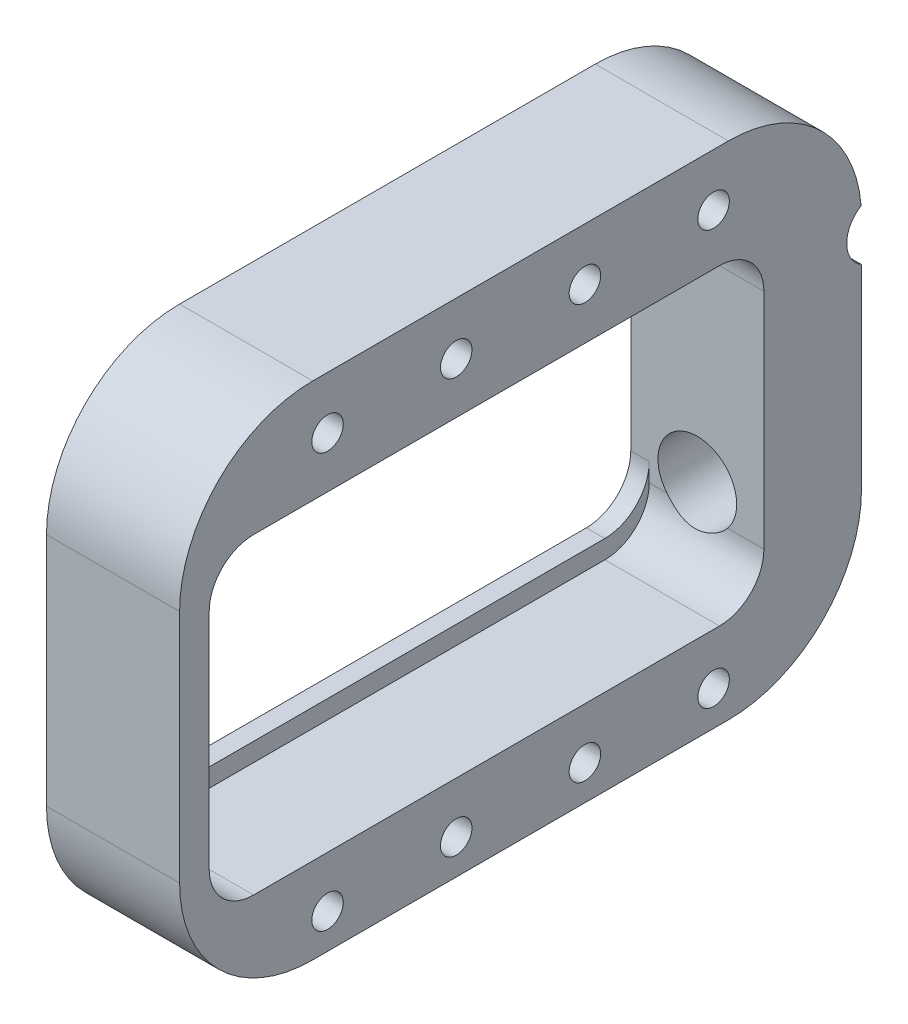
SolidWorks part; units mm, degrees
material "6061-T6 (SS)"
ref_plane "Front Plane" through (0, 0, 0) normal (0, 0, 1) x (1, 0, 0)
ref_plane "Top Plane" through (0, 0, 0) normal (0, 1, 0) x (1, 0, 0)
ref_plane "Right Plane" through (0, 0, 0) normal (1, 0, 0) x (0, 0, -1)
sketch "Sketch1" plane through (0, 0, 0) normal (1, 0, 0) x (0, 0, -1)
  line L0 (0, 22.2885) -> (0, -22.2885) construction
  line L1 (-26.3525, 22.2885) -> (32.1945, 22.2885)
  line L2 (-26.3525, 22.2885) -> (-26.3525, -22.2885)
  line L3 (-26.3525, -22.2885) -> (32.1945, -22.2885)
  line L4 (32.1945, 22.2885) -> (32.1945, -22.2885)
  line L5 (-23.8125, 13.3985) -> (23.8125, 13.3985)
  line L6 (-23.8125, 13.3985) -> (-23.8125, -13.3985)
  line L7 (-23.8125, -13.3985) -> (23.8125, -13.3985)
  line L8 (23.8125, 13.3985) -> (23.8125, -13.3985)
  line L9 (23.8125, -13.3985) -> (-23.8125, 13.3985) construction
  dimension "D1" = 8.89
  dimension "D2" = 2.54
  dimension "D3" = 47.625
  dimension "D4" = 26.797
  dimension "D5" = 8.382
  dimension "D6" = 8.89
extrude "Boss-Extrude1" add sketch "Sketch1" along normal mid plane 11.43
sketch "Sketch9" plane through (0, 0, -23.8125) normal (0, 0, 1) x (1, 0, 0)
  line L0 (-5.715, 13.3985) -> (-5.715, 11.811)
  line L1 (-5.715, -13.3985) -> (-4.1275, -13.3985)
  line L2 (-5.715, -13.3985) -> (-5.715, -11.811)
  line L3 (-5.715, -11.811) -> (-4.1275, -11.811)
  line L4 (-4.1275, -13.3985) -> (-4.1275, -11.811)
  line L5 (-5.715, 13.3985) -> (-4.1275, 13.3985)
  line L6 (-5.715, 11.811) -> (-4.1275, 11.811)
  line L7 (-4.1275, 13.3985) -> (-4.1275, 11.811)
  line L9 (-5.715, -13.3985) -> (-5.715, 13.3985) construction
  dimension "D1" = 23.622
  dimension "D2" = 1.5875
extrude "Boss-Extrude2" add sketch "Sketch9" along normal up to next
fillet "Fillet11" radius 3.81 4 edges at (-4.9213, -11.811, -23.8125) (-4.9212, 11.811, -23.8125) (-4.9213, -11.811, 23.8125) (-4.9212, 11.811, 23.8125)
fillet "Fillet12" radius 3.81 4 edges at (0.7937, 13.3985, 23.8125) (0.7937, -13.3985, 23.8125) (0.7938, -13.3985, -23.8125) (0.7937, 13.3985, -23.8125)
sketch "Sketch21" plane through (5.715, 0, 0) normal (1, 0, 0) x (0, 0, -1)
  line L1 (32.1945, 22.2885) -> (-26.3525, 22.2885) construction
  line L4 (32.1945, -22.2885) -> (32.1945, 22.2885) construction
  circle A0 centre (33.4645, 9.5885) radius 2.54
  dimension "D1" = 5.08
  dimension "D3" = 1.27
  dimension "D2" = 12.7
extrude "Cut-Extrude3" cut sketch "Sketch21" against normal blind 1.27
hole_wizard "1/4 Clearance Hole1" positions "Sketch5" profile "Sketch4" hole size "1/4" standard "ANSI Inch"
sketch "Sketch5" plane through (-2.5308, 6.493, -32.1945) normal (0, 0, 1) x (1, 0, 0)
  line L12 (8.2458, 15.7955) -> (8.2458, -28.7815) construction
  line L16 (-3.1842, -19.8915) -> (8.2458, -19.8915) construction
  line L17 (-3.1842, 15.7955) -> (-3.1842, -28.7815) construction
  line L30 (2.5308, -19.8915) -> (2.5308, -13.9225) construction
  line L32 (8.2458, -28.7815) -> (8.2458, 0.8958) construction
  point P0 (2.5308, -13.9225)
  dimension "D2" = 5.969
sketch "Sketch4" plane through (0, -7.4295, -32.1945) normal (1, 0, 0) x (0, 1, 0)
  line L0 (0, 0) -> (0, 10.9198)
  line L1 (0, 10.9198) -> (3.3782, 8.89)
  line L2 (3.3782, 8.89) -> (3.3782, 0)
  line L5 (3.3782, 0) -> (0, 0)
  line L10 (0, 10.9198) -> (-3.3782, 8.89) construction
  line L11 (0, -6.35) -> (0, 107.95) construction
  dimension "Hole Dia." = 6.7564
  dimension "Hole Depth" = 8.89
  dimension "Drill Angle" = 118
sketch "Sketch14" plane through (-5.715, 0, 0) normal (-1, 0, 0) x (0, 0, 1)
  line L0 (-32.1945, -17.78) -> (-19.4945, -17.78) construction
  line L1 (-32.1945, 17.78) -> (-19.4945, 17.78) construction
  line L2 (-19.4945, 17.78) -> (-8.4455, 17.78) construction
  line L3 (13.6525, 17.78) -> (26.3525, 17.78) construction
  line L4 (-19.4945, -17.78) -> (-8.4455, -17.78) construction
  line L5 (13.6525, -17.78) -> (26.3525, -17.78) construction
  line L6 (-19.1091, 17.78) -> (-19.1091, 22.2885) construction
  line L7 (-7.0267, -17.78) -> (-7.0267, -22.2885) construction
  line L8 (-8.4455, -17.78) -> (2.6035, -17.78) construction
  line L9 (2.6035, -17.78) -> (13.6525, -17.78) construction
  line L10 (2.6035, 17.78) -> (13.6525, 17.78) construction
  line L11 (-8.4455, 17.78) -> (2.6035, 17.78) construction
  line L12 (26.3525, -22.2885) -> (-32.1945, -22.2885) construction
  line L13 (-32.1945, 22.2885) -> (26.3525, 22.2885) construction
  line L14 (26.3525, 22.2885) -> (26.3525, -22.2885) construction
  line L15 (-32.1945, -22.2885) -> (-32.1945, 22.2885) construction
  point P0 (-19.4945, 17.78)
  point P1 (-19.4945, -17.78)
  point P2 (13.6525, -17.78)
  point P3 (13.6525, 17.78)
  dimension "D1" = 12.7
  dimension "D2" = 35.56
hole_wizard "#6-32 Tapped Hole1" positions "Sketch16" profile "Sketch15" tap size "#6-32" standard "ANSI Inch" end condition through all
sketch "Sketch16" plane through (5.715, 17.9556, 19.2123) normal (-1, 0, 0) x (0, 0, 1)
  point P0 (-27.6578, -0.1756)
  point P3 (-16.6088, -0.1756)
  point P6 (-5.5598, -0.1756)
  point P9 (-38.7068, -0.1756)
  point P12 (-38.7068, -35.7356)
  point P15 (-27.6578, -35.7356)
  point P18 (-16.6088, -35.7356)
  point P21 (-5.5598, -35.7356)
cosmetic thread "Hole Thread1" parameters "D2"=3.5052
cosmetic thread "Hole Thread2" parameters "D2"=3.5052
cosmetic thread "Hole Thread3" parameters "D2"=3.5052
cosmetic thread "Hole Thread4" parameters "D2"=3.5052
cosmetic thread "Hole Thread5" parameters "D2"=3.5052
cosmetic thread "Hole Thread6" parameters "D2"=3.5052
cosmetic thread "Hole Thread7" parameters "D2"=3.5052
cosmetic thread "Hole Thread8" parameters "D2"=3.5052
sketch "Sketch15" plane through (5.715, 17.78, -8.4455) normal (0, 1, 0) x (0, 0, -1)
  line L0 (0, 0) -> (0, 11.43)
  line L1 (0, 11.43) -> (1.3525, 11.43)
  line L2 (1.3525, 11.43) -> (1.3525, 0)
  line L5 (1.3525, 0) -> (0, 0)
  line L11 (0, -6.35) -> (0, 107.95) construction
  dimension "Thru Tap Drill Dia." = 2.7051
  dimension "Thru Tap Drill Depth" = 11.43
sketch "Sketch22" plane through (5.715, 0, 0) normal (1, 0, 0) x (0, 0, -1)
  line L0 (-26.3525, 22.2885) -> (-26.3525, -22.2885) construction
  line L1 (-26.3525, -28.2057) -> (32.1945, -28.2057)
  line L2 (-26.3525, -28.2057) -> (-26.3525, -20.7645)
  line L3 (-26.3525, -20.7645) -> (32.1945, -20.7645)
  line L4 (32.1945, -28.2057) -> (32.1945, -20.7645)
  line L5 (-26.3525, -28.2057) -> (32.1945, -20.7645) construction
  line L6 (-26.3525, -20.7645) -> (32.1945, -28.2057) construction
  line L7 (32.1945, -22.2885) -> (32.1945, 7.3888) construction
  line L8 (-26.3525, -22.2885) -> (32.1945, -22.2885) construction
  point P4 (2.921, -24.4851)
  dimension "D1" = 1.524
extrude "Cut-Extrude4" cut sketch "Sketch22" against normal through all
fillet "Fillet13" radius 11.43 2 edges at (0, 22.2885, -32.1945) (0, -20.7645, -32.1945)
fillet "Fillet14" radius 11.43 2 edges at (0, 22.2885, 26.3525) (0, -20.7645, 26.3525)
sketch "Sketch11" plane through (5.715, 0, 0) normal (1, 0, 0) x (0, 0, -1)
  line L0 (32.1945, -9.3345) -> (32.1945, 7.3888) construction
  line L1 (32.1945, 16.2163) -> (30.861, 16.2163)
  line L2 (32.1945, 16.2163) -> (32.1945, -14.6923)
  line L3 (32.1945, -14.6923) -> (30.861, -14.6923)
  line L4 (30.861, 16.2163) -> (30.861, -14.6923)
  arc A1 (32.1583, 11.7669) -> (20.7645, 22.2885) centre (20.7645, 10.8585) ccw construction
  arc A2 (20.7645, -20.7645) -> (32.1945, -9.3345) centre (20.7645, -9.3345) ccw construction
  dimension "D1" = 30.861
extrude "Cut-Extrude2" [suppressed] cut sketch "Sketch11" against normal blind 1.016
ref_point "Point1" [suppressed]
sketch "Sketch17" plane through (-5.715, 0, 0) normal (-1, 0, 0) x (0, 0, 1)
  line L0 (-44.2595, 38.862) -> (-44.2595, -37.338)
  line L1 (-44.2595, 38.862) -> (116.0145, 38.862)
  line L2 (-44.2595, -37.338) -> (116.0145, -37.338)
  line L3 (116.0145, 38.862) -> (116.0145, -37.338)
  line L4 (45.4025, 22.2885) -> (45.4025, -20.7645) construction
  line L5 (45.4025, 22.2885) -> (103.9495, 22.2885) construction
  line L6 (45.4025, -20.7645) -> (103.9495, -20.7645) construction
  line L7 (103.9495, 22.2885) -> (103.9495, -20.7645) construction
  line L8 (-32.1945, 0.762) -> (26.3525, 0.762) construction
  line L10 (26.3525, 10.8585) -> (26.3525, -9.3345) construction
  line L11 (-32.1945, 0.762) -> (-44.2595, 0.762) construction
  line L12 (-20.7645, 22.2885) -> (14.9225, 22.2885) construction
  line L14 (103.9495, 0.762) -> (116.0145, 0.762) construction
  line L15 (-44.2595, -37.338) -> (-40.3225, -41.275) construction
  line L16 (-40.3225, -41.275) -> (112.0775, -41.275) construction
  line L17 (112.0775, -41.275) -> (116.0145, -37.338) construction
  line L18 (-40.3225, -41.275) -> (-40.3225, -37.338) construction
  line L19 (112.0775, -41.275) -> (112.0775, -37.338) construction
  line L20 (26.3525, 10.8585) -> (26.3525, -9.3345) construction
  line L21 (-32.1945, -9.3345) -> (-32.1945, 10.8585) construction
  line L22 (-20.7645, -20.7645) -> (14.9225, -20.7645) construction
  dimension "D1" = 19.05
  dimension "D2" = 76.2
  dimension "D3" = 152.4
  dimension "D4" = 12.065
extrude "Maching Stock" [suppressed] add sketch "Sketch17" against normal blind 12.7 separate body
sketch "Sketch19" [suppressed] plane through (-5.715, 0, 0) normal (-1, 0, 0) x (0, 0, 1)
  line L0 (-8.001, 35.0972) -> (-8.001, -32.2156) construction
  line L1 (-8.001, -32.2156) -> (2.159, -32.2156) construction
  line L2 (2.159, -32.2156) -> (2.159, 32.3464) construction
  line L3 (34.7223, 0.127) -> (-40.8428, 0.127) construction
  line L4 (26.3525, -9.3345) -> (26.3525, 10.8585)
  line L5 (14.9225, 22.2885) -> (-20.7645, 22.2885)
  line L6 (-32.1945, 10.8585) -> (-32.1945, -9.3345)
  line L7 (-20.7645, -20.7645) -> (14.9225, -20.7645)
  line L8 (26.3525, -9.3345) -> (26.3525, -10.033)
  line L9 (14.9225, 22.2885) -> (2.159, 22.2885)
  line L10 (-32.1945, 10.8585) -> (-32.1945, 0.127)
  line L11 (-20.7645, -20.7645) -> (14.9225, -20.7645)
  line L12 (-40.8428, 0.127) -> (-40.8428, -10.033) construction
  line L13 (-40.8428, -10.033) -> (36.1785, -10.033) construction
  line L14 (2.159, -22.2885) -> (14.9225, -22.2885)
  line L15 (-8.001, 22.2885) -> (-20.7645, 22.2885)
  line L16 (26.3525, 0.127) -> (26.3525, 10.8585)
  line L17 (-32.1945, -10.033) -> (-32.1945, 0.6985)
  arc A3 (-32.1945, -9.3345) -> (-20.7645, -20.7645) centre (-20.7645, -9.3345) ccw
  arc A4 (26.3525, 10.8585) -> (14.9225, 22.2885) centre (14.9225, 10.8585) ccw
  arc A5 (-20.7645, 22.2885) -> (-32.1945, 10.8585) centre (-20.7645, 10.8585) ccw
  arc A6 (-32.1945, -9.3345) -> (-20.7645, -20.7645) centre (-20.7645, -9.3345) ccw
  arc A8 (26.3525, 10.8585) -> (14.9225, 22.2885) centre (14.9225, 10.8585) ccw
  arc A9 (-20.7645, 22.2885) -> (-32.1945, 10.8585) centre (-20.7645, 10.8585) ccw
  arc A10 (14.9225, -20.7645) -> (26.3525, -9.3345) centre (14.9225, -9.3345) ccw
  arc A11 (14.9225, -20.7645) -> (26.3525, -9.3345) centre (14.9225, -9.3345) ccw
  dimension "D2" = 10.16
  dimension "D1" = 0
sketch "Sketch20" plane through (5.715, 0, 0) normal (-1, 0, 0) x (0, 0, 1)
  line L0 (26.3525, 22.2885) -> (-125.3109, 22.2885) construction
  line L1 (26.3525, 10.8585) -> (26.3525, -9.3345) construction
  line L3 (-20.7645, 22.2885) -> (14.9225, 22.2885) construction
  dimension "D1" = 151.6634
ref_point "Point2"
ref_point "Point3"
